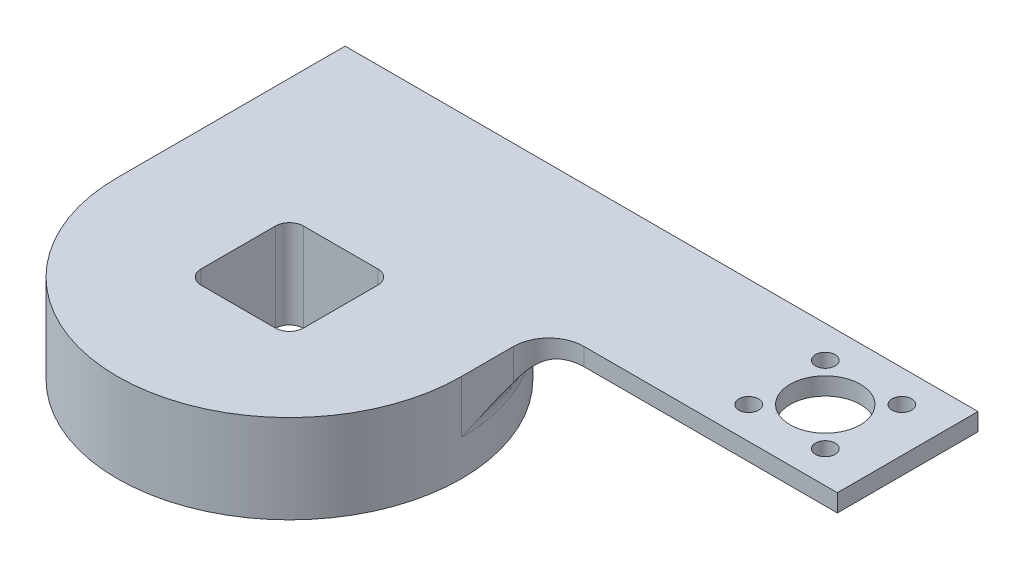
SolidWorks part; units mm, degrees
material "6061-T6 (SS)"
ref_plane "Front Plane" through (0, 0, 0) normal (0, 0, 1) x (1, 0, 0)
ref_plane "Top Plane" through (0, 0, 0) normal (0, 1, 0) x (1, 0, 0)
ref_plane "Right Plane" through (0, 0, 0) normal (1, 0, 0) x (0, 0, -1)
sketch "Sketch1" plane through (0, 0, 0) normal (0, 1, 0) x (1, 0, 0)
  line L0 (-1.1049, 0) -> (-31.0896, 0) construction
  line L1 (-1.1049, 0) -> (31.0896, 0) construction
  circle A0 centre (0, 0) radius 31.0896
  dimension "D1" = 62.1792
extrude "Boss-Extrude1" add sketch "Sketch1" along normal blind 16.002
sketch "Sketch2" plane through (0, 16.002, 0) normal (0, 1, 0) x (1, 0, 0)
  line L0 (0, 0) -> (-31.0896, 0) construction
  line L1 (0, 0) -> (31.0896, 0) construction
  line L2 (-31.0896, 0) -> (-31.0896, 41.148)
  line L3 (-31.0896, 41.148) -> (83.2104, 41.148)
  line L4 (83.2104, 41.148) -> (83.2104, 15.748)
  line L5 (31.0896, 0) -> (31.0896, 15.748)
  line L6 (31.0896, 15.748) -> (83.2104, 15.748)
  circle A0 centre (0, 0) radius 31.0896 construction
  circle A2 centre (0, 0) radius 31.0896
  arc A3 (-31.0896, 0) -> (31.0896, 0) centre (0, 0) ccw
  dimension "D1" = 0
  dimension "D2" = 114.3
  dimension "D3" = 25.4
  dimension "D4" = 15.748
extrude "Boss-Extrude2" add sketch "Sketch2" against normal blind 3.175
fillet "Fillet1" radius 6.35 1 edges at (0, 12.827, -31.0896)
fillet "Fillet2" radius 6.35 1 edges at (31.0896, 14.1386, -15.748)
sketch "Sketch4" plane through (0, 16.002, 0) normal (0, 1, 0) x (1, 0, 0)
  line L0 (83.2104, 41.148) -> (58.166, 41.148) construction
  line L1 (83.2104, 41.148) -> (-31.0896, 41.148) construction
  line L2 (58.166, 41.148) -> (58.166, 28.448) construction
  line L3 (58.166, 28.448) -> (78.486, 28.448) construction
  line L4 (68.326, 28.448) -> (75.2408, 35.3628) construction
  line L5 (68.326, 28.448) -> (75.2408, 21.5332) construction
  line L6 (68.326, 28.448) -> (61.4112, 21.5332) construction
  line L7 (68.326, 28.448) -> (61.4112, 35.3628) construction
  circle A0 centre (61.4112, 35.3628) radius 1.778
  circle A1 centre (75.2408, 35.3628) radius 1.778
  circle A2 centre (75.2408, 21.5332) radius 1.778
  circle A3 centre (68.326, 28.448) radius 6.35
  circle A4 centre (61.4112, 21.5332) radius 1.778
extrude "Cut-Extrude2" cut sketch "Sketch4" against normal up to next
sketch "Sketch5" plane through (0, 16.002, 0) normal (0, 1, 0) x (1, 0, 0)
  line L1 (9.2497, 9.2497) -> (-9.2497, 9.2497)
  line L2 (9.2497, 9.2497) -> (9.2497, -9.2497)
  line L3 (9.2497, -9.2497) -> (-9.2497, -9.2497)
  line L4 (-9.2497, 9.2497) -> (-9.2497, -9.2497)
  line L5 (9.2497, 9.2497) -> (-9.2497, -9.2497) construction
  line L6 (9.2497, -9.2497) -> (-9.2497, 9.2497) construction
  point P0 (0, 0)
  dimension "D1" = 26.162
extrude "Cut-Extrude3" cut sketch "Sketch5" against normal up to next
fillet "Fillet3" radius 2.54 1 edges at (-9.2497, 8.001, -9.2497)
fillet "Fillet4" radius 2.54 1 edges at (9.2497, 8.001, -9.2497)
fillet "Fillet5" radius 2.54 1 edges at (9.2497, 8.001, 9.2497)
fillet "Fillet6" radius 2.54 1 edges at (-9.2497, 8.001, 9.2497)
